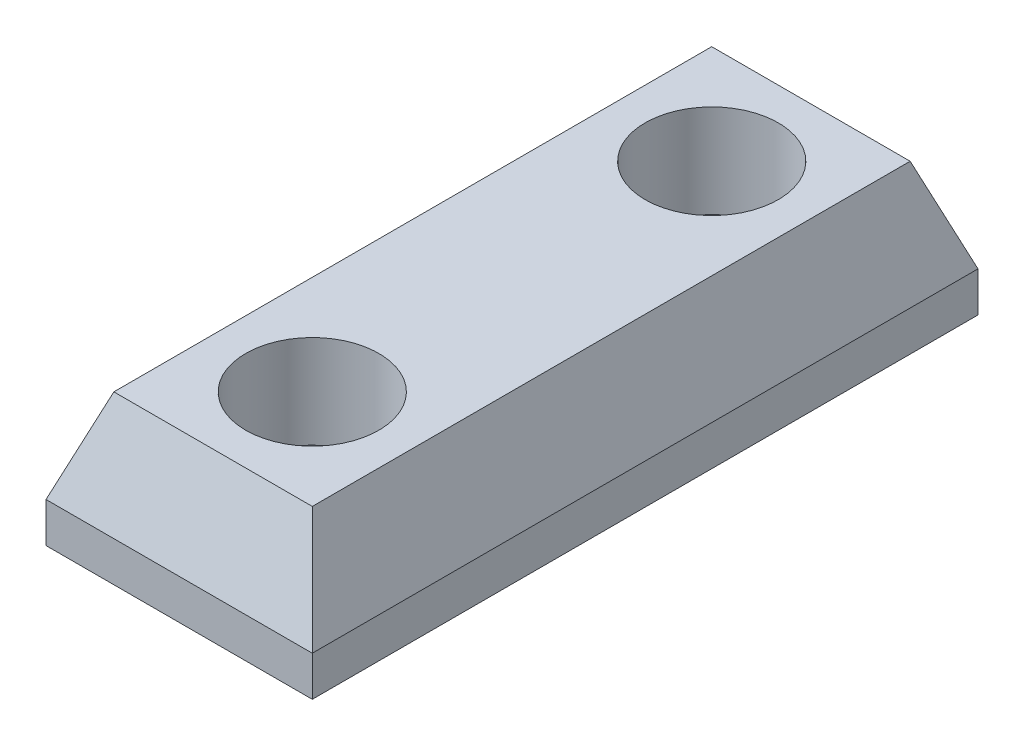
SolidWorks part; units mm, degrees
ref_plane "Front Plane" through (0, 0, 0) normal (0, 0, 1) x (1, 0, 0)
ref_plane "Top Plane" through (0, 0, 0) normal (0, 1, 0) x (1, 0, 0)
ref_plane "Right Plane" through (0, 0, 0) normal (1, 0, 0) x (0, 0, -1)
sketch "Sketch1" plane through (0, 0, 0) normal (0, 1, 0) x (1, 0, 0)
  line L0 (-10, 10) -> (-10, 40) construction
  line L1 (0, 0) -> (-20, 0)
  line L2 (0, 0) -> (0, 50)
  line L3 (0, 50) -> (-20, 50)
  line L4 (-20, 0) -> (-20, 50)
  circle A0 centre (-10, 40) radius 2.5
  circle A1 centre (-10, 10) radius 2.5
  circle A2 centre (-10, 40) radius 5
  circle A3 centre (-10, 10) radius 5
  point P9 (-10, 25)
  point P10 (0, 25)
  point P11 (-10, 50)
  dimension "D2" = 5
  dimension "D5" = 10
  dimension "D1" = 20
  dimension "D3" = 30
  dimension "D4" = 10
extrude "Boss-Extrude1" add sketch "Sketch1" along normal blind 3 contours A2 A0 | A1 A3 region at (-14.8586, 0, -40) region at (-14.8586, 0, -10)
extrude "Boss-Extrude2" add sketch "Sketch1<3>" along normal blind 10 contours L4 L1 L2 L3 A3 A2 region at (-10, 0, -25)
sketch "Sketch1<3>" plane through (0, 0, 0) normal (0, 1, 0) x (1, 0, 0) same geometry as "Sketch1"
chamfer "Chamfer1" distance 7 angle 20 4 edges at (-10, 10, -50) (-20, 10, -25) (-10, 10, 0) (0, 10, -25) first distance on face at (-10, 5, -50) first distance on face at (-20, 5, -25) first distance on face at (-10, 5, 0) first distance on face at (0, 5, -25)
